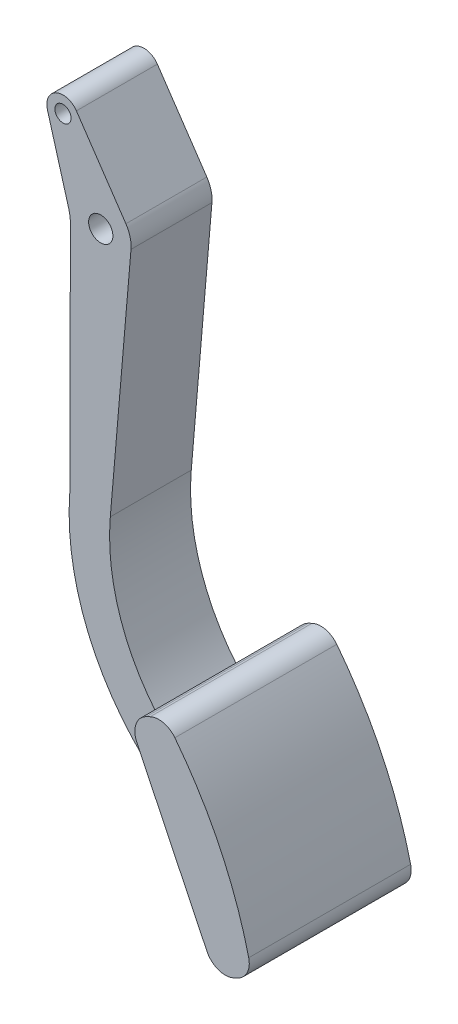
SolidWorks part; units mm, degrees
note: The reader was unsure of these and kept them because the rebuilt part matched: shared geometry of "Sketch1<4>".
ref_plane "Front Plane" through (0, 0, 0) normal (0, 0, 1) x (1, 0, 0)
ref_plane "Top Plane" through (0, 0, 0) normal (0, 1, 0) x (1, 0, 0)
ref_plane "Right Plane" through (0, 0, 0) normal (1, 0, 0) x (0, 0, -1)
sketch "Sketch1" plane through (0, 0, 0) normal (0, 0, 1) x (1, 0, 0)
  line L0 (0, 60) -> (0, -60) construction
  line L1 (0, 60) -> (-18.6523, 60) construction
  line L2 (0, 40) -> (-49.8694, 40)
  line L3 (0, -20) -> (-5.2393, -20) construction
  line L4 (0, -60) -> (-52.6666, -60) construction
  line L5 (0, 40) -> (-9.3262, 60) construction
  line L6 (0, 40) -> (-2.6197, -20) construction
  line L7 (-6.0149, 62.2441) -> (6.2086, 44.2076)
  line L8 (-13.1736, 58.9059) -> (-7.5021, 38.9617)
  line L9 (7.4727, 39.3612) -> (2.3622, -20.4258)
  line L10 (-7.5, 40.015) -> (-7.5, 40)
  line L11 (24, -8.15) -> (24, -67.3109) construction
  line L12 (24, -65.9863) -> (31.1619, -80.8823)
  line L13 (-7.5021, 38.9617) -> (-7.6192, -19.7863)
  line L14 (24, -65.9863) -> (16.7481, -50.9033)
  line L15 (31.1619, -80.8823) -> (38.4138, -95.9654)
  line L16 (16.7481, -50.9033) -> (25.7605, -46.5701)
  line L17 (38.4138, -95.9654) -> (47.4263, -91.6323)
  arc A0 (-6.0149, 62.2441) -> (-13.1736, 58.9059) centre (-9.3262, 60) ccw
  arc A1 (7.4727, 39.3612) -> (6.2086, 44.2076) centre (0, 40) ccw
  arc A3 (2.3622, -20.4258) -> (24, -65.9863) centre (52.1805, -24.6843) ccw
  arc A5 (-7.6192, -19.7863) -> (31.1619, -80.8823) centre (52.1805, -24.6843) ccw
  arc A6 (-0.3271, 32.5071) -> (0, 32.5) centre (0, 40) ccw
  arc A7 (-7.5, 40.015) -> (-7.5, 40) centre (0, 40) ccw
  arc A8 (25.7605, -46.5701) -> (47.4263, -91.6323) centre (-50.6691, -111.0567) cw
  point P4 (0, 0)
  point P10 (27.581, -73.4343)
  dimension "D6" = 8
  dimension "D7" = 15
  dimension "D8" = 10
  dimension "D10" = 50
  dimension "D1" = 60
  dimension "D2" = 100
  dimension "D3" = 20
  dimension "D4" = 25
  dimension "D5" = 2.5
  dimension "D9" = 24
  dimension "D11" = 10
  dimension "D12" = 50
  dimension "D13" = 25
extrude "Boss-Extrude3" add sketch "Sketch1" along normal mid plane 20
extrude "Boss-Extrude4" add sketch "Sketch1<4>" along normal mid plane 40 contours A8 L16 L14 L12 L15 L17
sketch "Sketch1<4>" plane through (0, 0, 0) normal (0, 0, 1) x (1, 0, 0) same geometry as "Sketch1"
sketch "Sketch2" plane through (0, 0, 10) normal (0, 0, 1) x (1, 0, 0)
  circle A0 centre (-9.3262, 60) radius 2
  circle A1 centre (0, 40) radius 3
  dimension "D1" = 4
  dimension "D2" = 6
extrude "Cut-Extrude1" cut sketch "Sketch2" against normal blind 40
fillet "Fillet3" radius 10 1 edges at (-7.5021, 38.9617, 0)
fillet "Fillet4" radius 10 1 edges at (-7.6192, -19.7863, 0)
fillet "Fillet5" radius 5 1 edges at (25.7605, -46.5701, 0)
fillet "Fillet6" radius 5 1 edges at (47.4263, -91.6323, 0)
fillet "Fillet7" radius 5 1 edges at (16.7481, -50.9033, 0)
fillet "Fillet8" radius 5 1 edges at (38.4138, -95.9654, 0)
